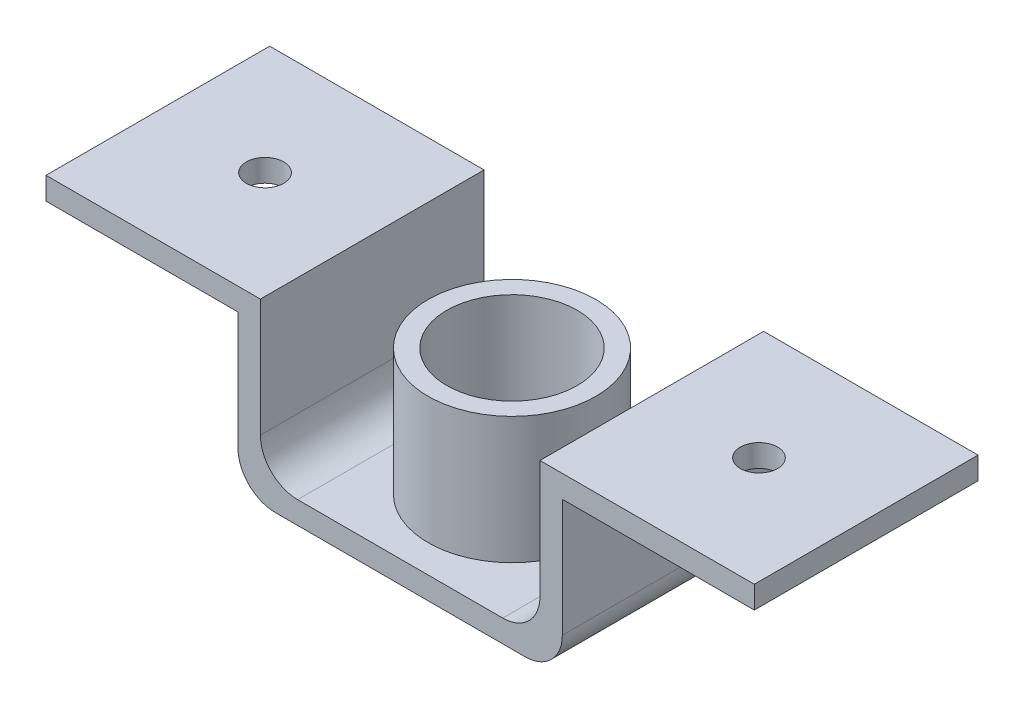
SolidWorks part; units mm, degrees
ref_plane "Front Plane" through (0, 0, 0) normal (0, 0, 1) x (1, 0, 0)
ref_plane "Top Plane" through (0, 0, 0) normal (0, 1, 0) x (1, 0, 0)
ref_plane "Right Plane" through (0, 0, 0) normal (1, 0, 0) x (0, 0, -1)
sketch "Sketch1" plane through (0, 0, 0) normal (0, 0, 1) x (1, 0, 0)
  line L0 (0, 0) -> (287.5, 0)
  line L1 (287.5, 0) -> (287.5, -158)
  line L2 (337.5, -208) -> (612.5, -208)
  line L3 (662.5, -158) -> (662.5, 0)
  line L4 (662.5, 0) -> (950, 0)
  line L5 (0, -30) -> (257.5, -30)
  line L6 (257.5, -30) -> (257.5, -188)
  line L7 (307.5, -238) -> (642.5, -238)
  line L8 (692.5, -188) -> (692.5, -30)
  line L9 (692.5, -30) -> (950, -30)
  line L10 (0, 0) -> (0, -30)
  line L11 (950, 0) -> (950, -30)
  line L12 (287.5, -208) -> (662.5, -208) construction
  line L13 (662.5, -208) -> (662.5, 0) construction
  line L14 (287.5, 0) -> (287.5, -208) construction
  line L15 (257.5, -238) -> (692.5, -238) construction
  line L16 (692.5, -238) -> (692.5, -30) construction
  line L17 (257.5, -30) -> (257.5, -238) construction
  arc A0 (612.5, -208) -> (662.5, -158) centre (612.5, -158) ccw
  arc A1 (287.5, -158) -> (337.5, -208) centre (337.5, -158) ccw
  arc A2 (642.5, -238) -> (692.5, -188) centre (642.5, -188) ccw
  arc A3 (257.5, -188) -> (307.5, -238) centre (307.5, -188) ccw
  point P16 (662.5, -208)
  dimension "D5" = 50
  dimension "D1" = 950
  dimension "D2" = 375
  dimension "D4" = 30
extrude "Boss-Extrude1" add sketch "Sketch1" along normal blind 300
sketch "Sketch3" plane through (0, 0, 0) normal (0, 1, 0) x (1, 0, 0)
  line L0 (0, 0) -> (287.5, -300) construction
  line L1 (475, 0) -> (475, -300) construction
  line L2 (612.5, 0) -> (337.5, 0) construction
  line L3 (612.5, -300) -> (337.5, -300) construction
  circle A0 centre (143.75, -150) radius 25
  circle A1 centre (806.25, -150) radius 25
  circle A2 centre (475, -150) radius 112.5
  circle A3 centre (475, -150) radius 87.5
  circle A4 centre (475, -150) radius 37.5
  dimension "D1" = 50
  dimension "D2" = 225
  dimension "D3" = 175
  dimension "D4" = 75
extrude "Cut-Extrude1" cut sketch "Sketch3" against normal through all contours A0 | A1 region at (143.75, 0, 150) region at (806.25, 0, 150)
extrude "Boss-Extrude2" add sketch "Sketch3<3>" along normal blind 170 from surface separate body contours A2 A3 region at (365.682, 0, 150) starting at face at (475, -208, 150)
sketch "Sketch3<3>" plane through (0, 0, 0) normal (0, 1, 0) x (1, 0, 0) same geometry as "Sketch3"
extrude "Cut-Extrude2" cut sketch "Sketch3<6>" against normal through all contours A4 region at (475, 0, 150)
sketch "Sketch3<6>" plane through (0, 0, 0) normal (0, 1, 0) x (1, 0, 0) same geometry as "Sketch3"
